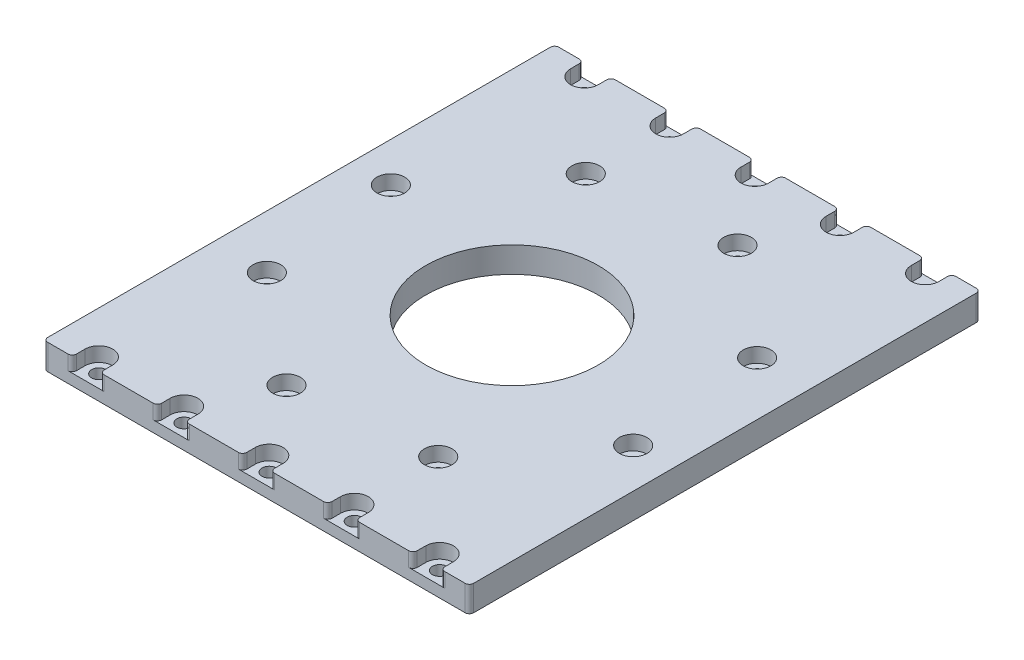
SolidWorks part; units mm, degrees
material "6061-T6 (SS)"
ref_plane "Front Plane" through (0, 0, 0) normal (0, 0, 1) x (1, 0, 0)
ref_plane "Top Plane" through (0, 0, 0) normal (0, 1, 0) x (1, 0, 0)
ref_plane "Right Plane" through (0, 0, 0) normal (1, 0, 0) x (0, 0, -1)
sketch "Sketch1" plane through (0, 0, 0) normal (0, 1, 0) x (1, 0, 0)
  circle A0 centre (0, 0) radius 50
  circle A1 centre (0, 0) radius 20.25
  dimension "D1" = 100
  dimension "D2" = 40.5
extrude "Boss-Extrude1" add sketch "Sketch1" along normal blind 6
sketch "Sketch2" plane through (0, 6, 0) normal (0, 1, 0) x (1, 0, 0)
  line L1 (-20.1161, 37.4379) -> (0, 0) construction
  circle A0 centre (0, 0) radius 42.5 construction
  point P4 (-20.1161, 37.4379)
  point P10 (12.2483, 40.6968)
  point P11 (37.4379, 20.1161)
  point P12 (40.6968, -12.2483)
  point P13 (20.1161, -37.4379)
  point P14 (-12.2483, -40.6968)
  point P15 (-37.4379, -20.1161)
  point P16 (-40.6968, 12.2483)
  dimension "D1" = 85
  dimension "D3" = 28.25
  dimension "D2" = 8
hole_wizard "CBORE for M3 Hex Socket Head Cap Screw2" positions "Sketch2" profile "Sketch3" counterbore size "M3" standard "DIN" end condition through all
sketch "Sketch3" plane through (-40.6968, 6, -12.2483) normal (1, 0, 0) x (0, 0, 1)
  line L0 (0, 0) -> (0, 6)
  line L1 (0, 6) -> (1.7, 6)
  line L3 (1.7, 6) -> (1.7, 3.4)
  line L4 (1.7, 3.4) -> (3.25, 3.4)
  line L5 (3.25, 3.4) -> (3.25, 0)
  line L7 (3.25, 0) -> (0, 0)
  line L11 (0, -6.35) -> (0, 107.95) construction
  dimension "Thru Hole Dia." = 3.4
  dimension "Thru Hole Depth" = 6
  dimension "C'Bore Dia." = 6.5
  dimension "C'Bore Depth" = 3.4
sketch "Sketch6" plane through (0, 6, 0) normal (0, 1, 0) x (1, 0, 0)
  line L0 (-50, 0) -> (-50, -60)
  line L1 (-50, -60) -> (50, -60)
  line L2 (50, -60) -> (50, 0)
  circle A0 centre (0, 0) radius 50 construction
  arc A1 (-50, 0) -> (50, 0) centre (0, 0) ccw
  dimension "D1" = 60
extrude "Boss-Extrude2" add sketch "Sketch6" against normal up to surface (6 mm away) up to face at (-20.1161, 0, -35.7379)
sketch "Sketch10" plane through (0, 6, 0) normal (0, 1, 0) x (1, 0, 0)
  line L0 (-50, 0) -> (-50, 60)
  line L1 (-50, 60) -> (50, 60)
  line L2 (50, 60) -> (50, 0)
  arc A0 (50, 0) -> (-50, 0) centre (0, 0) ccw construction
  arc A1 (50, 0) -> (-50, 0) centre (0, 0) ccw
  dimension "D1" = 60
extrude "Boss-Extrude3" add sketch "Sketch10" against normal up to surface (6 mm away) up to face at (-20.1161, 0, -35.7379)
sketch "Sketch11" plane through (0, 6, 0) normal (0, 1, 0) x (1, 0, 0)
  line L0 (50, 60) -> (-50, 60) construction
  line L3 (0, 0) -> (0, 57) construction
  line L4 (0, 0) -> (-50000, 0) construction
  point P0 (-40, 57)
  point P13 (-20, 57)
  point P14 (0, 57)
  point P15 (20, 57)
  point P16 (40, 57)
  point P57 (40, -57)
  point P58 (20, -57)
  point P59 (0, -57)
  point P60 (-20, -57)
  point P61 (-40, -57)
  dimension "D1" = 3
  dimension "D2" = 5
  dimension "D5" = 20
hole_wizard "CBORE for M3 Hex Socket Head Cap Screw1" positions "Sketch11" profile "Sketch12" counterbore size "M3" standard "DIN" end condition through all
sketch "Sketch12" plane through (-40, 6, -57) normal (1, 0, 0) x (0, 0, 1)
  line L0 (0, 0) -> (0, 6)
  line L1 (0, 6) -> (1.7, 6)
  line L3 (1.7, 6) -> (1.7, 3.4)
  line L4 (1.7, 3.4) -> (3.25, 3.4)
  line L5 (3.25, 3.4) -> (3.25, 0)
  line L7 (3.25, 0) -> (0, 0)
  line L11 (0, -6.35) -> (0, 107.95) construction
  dimension "Thru Hole Dia." = 3.4
  dimension "Thru Hole Depth" = 6
  dimension "C'Bore Dia." = 6.5
  dimension "C'Bore Depth" = 3.4
sketch "Sketch13" plane through (0, 6, 0) normal (0, 1, 0) x (1, 0, 0)
  line L0 (-43.25, 57) -> (-43.25, 60)
  line L1 (-41.25, 60) -> (-50, 60) construction
  line L2 (-43.25, 60) -> (-36.75, 60)
  line L3 (-21.25, 60) -> (-38.75, 60) construction
  line L4 (-36.75, 60) -> (-36.75, 57)
  line L5 (-23.25, 57) -> (-23.25, 60)
  line L6 (-23.25, 60) -> (-16.75, 60)
  line L7 (-16.75, 60) -> (-16.75, 57)
  line L8 (-3.25, 57) -> (-3.25, 60)
  line L9 (-3.25, 60) -> (3.25, 60)
  line L10 (3.25, 60) -> (3.25, 57)
  line L11 (16.75, 57) -> (16.75, 60)
  line L12 (16.75, 60) -> (23.25, 60)
  line L13 (23.25, 60) -> (23.25, 57)
  line L14 (36.75, 57) -> (36.75, 60)
  line L15 (36.75, 60) -> (43.25, 60)
  line L16 (43.25, 60) -> (43.25, 57)
  line L17 (0, 0) -> (69.1463, 0) construction
  line L18 (43.25, -60) -> (43.25, -57)
  line L19 (36.75, -60) -> (43.25, -60)
  line L20 (36.75, -57) -> (36.75, -60)
  line L21 (23.25, -60) -> (23.25, -57)
  line L22 (16.75, -60) -> (23.25, -60)
  line L23 (16.75, -57) -> (16.75, -60)
  line L24 (3.25, -60) -> (3.25, -57)
  line L25 (-3.25, -60) -> (3.25, -60)
  line L26 (-3.25, -57) -> (-3.25, -60)
  line L27 (-16.75, -60) -> (-16.75, -57)
  line L28 (-23.25, -60) -> (-16.75, -60)
  line L29 (-23.25, -57) -> (-23.25, -60)
  line L30 (-36.75, -60) -> (-36.75, -57)
  line L31 (-43.25, -60) -> (-36.75, -60)
  line L32 (-43.25, -57) -> (-43.25, -60)
  arc A0 (-41.25, 60) -> (-38.75, 60) centre (-40, 57) ccw construction
  arc A1 (-43.25, 57) -> (-36.75, 57) centre (-40, 57) ccw
  arc A2 (-23.25, 57) -> (-16.75, 57) centre (-20, 57) ccw
  arc A3 (-3.25, 57) -> (3.25, 57) centre (0, 57) ccw
  arc A4 (16.75, 57) -> (23.25, 57) centre (20, 57) ccw
  arc A5 (36.75, 57) -> (43.25, 57) centre (40, 57) ccw
  arc A6 (36.75, -57) -> (43.25, -57) centre (40, -57) cw
  arc A7 (16.75, -57) -> (23.25, -57) centre (20, -57) cw
  arc A8 (-3.25, -57) -> (3.25, -57) centre (0, -57) cw
  arc A9 (-23.25, -57) -> (-16.75, -57) centre (-20, -57) cw
  arc A10 (-43.25, -57) -> (-36.75, -57) centre (-40, -57) cw
  dimension "D1" = 5
extrude "Cut-Extrude1" cut sketch "Sketch13" against normal up to surface (3.4 mm away) up to face at (-40, 2.6, -56.875)
fillet "Fillet1" radius 1 24 edges at (-43.25, 4.3, 60) (-50, 3, 60) (-50, 3, -60) (-36.75, 4.3, -60) (-23.25, 4.3, -60) (-16.75, 4.3, -60) (-3.25, 4.3, -60) (3.25, 4.3, -60) (16.75, 4.3, -60) (23.25, 4.3, -60) (36.75, 4.3, -60) (43.25, 4.3, -60) (50, 3, -60) (50, 3, 60) (43.25, 4.3, 60) (36.75, 4.3, 60) (23.25, 4.3, 60) (16.75, 4.3, 60) (3.25, 4.3, 60) (-3.25, 4.3, 60) (-16.75, 4.3, 60) (-23.25, 4.3, 60) (-36.75, 4.3, 60) (-43.25, 4.3, -60)
